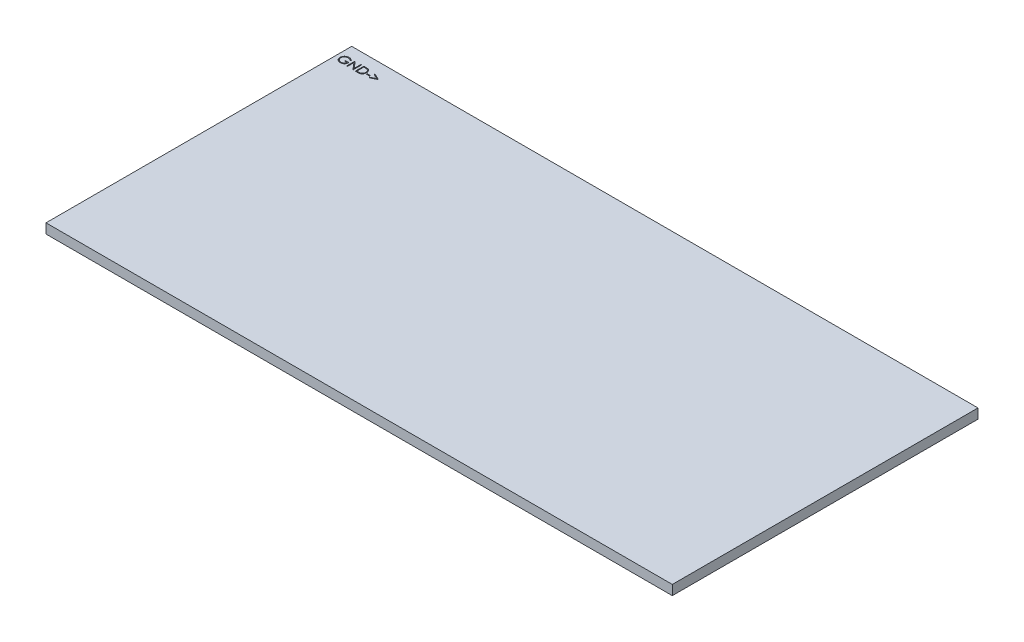
SolidWorks part; units mm, degrees
ref_plane "Front Plane" through (0, 0, 0) normal (0, 0, 1) x (1, 0, 0)
ref_plane "Top Plane" through (0, 0, 0) normal (0, 1, 0) x (1, 0, 0)
ref_plane "Right Plane" through (0, 0, 0) normal (1, 0, 0) x (0, 0, -1)
sketch "Sketch1" plane through (0, 0, 0) normal (0, 1, 0) x (1, 0, 0)
  line L1 (0, 0) -> (102, 0)
  line L2 (0, 0) -> (0, 49.784)
  line L3 (0, 49.784) -> (102, 49.784)
  line L4 (102, 0) -> (102, 49.784)
  point P7 (6.858, 47.244)
extrude "Boss-Extrude1" add sketch "Sketch1" along normal blind 1.5875
sketch "Sketch2" plane through (0, 1.5875, 0) normal (0, 1, 0) x (1, 0, 0)
  text T0 "GND->" font "Century Gothic" height 1.4
  point P1 (6.858, 47.244)
extrude "Cut-Extrude1" cut sketch "Sketch2" against normal blind 0.2
sketch "Sketch5" plane through (0, 0, 0) normal (0, -1, 0) x (1, 0, 0)
  line L0 (101.1416, -7.6744) -> (94.742, -7.6744) construction
  text T2 "GND->" font "Century Gothic" height 1.4
  point P6 (0, 0)
  point P7 (94.742, -8.382)
extrude "Cut-Extrude2" cut sketch "Sketch5" against normal blind 0.2
